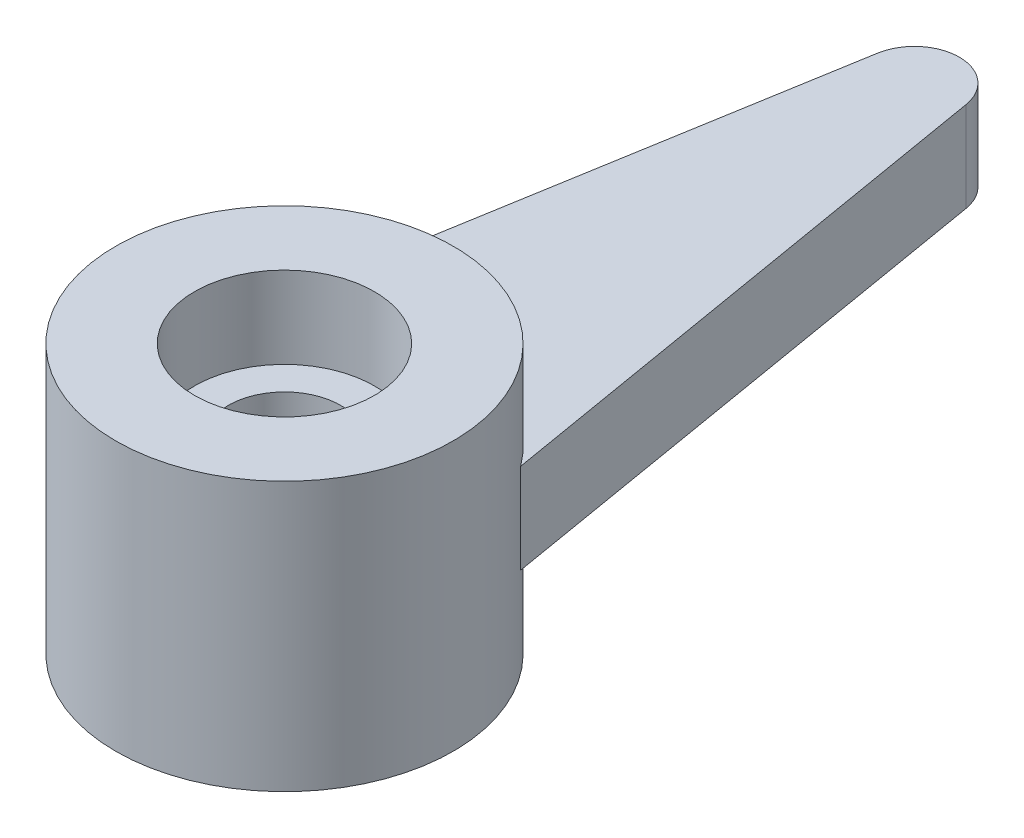
SolidWorks part; units mm, degrees
ref_plane "Front Plane" through (0, 0, 0) normal (0, 0, 1) x (1, 0, 0)
ref_plane "Top Plane" through (0, 0, 0) normal (0, 1, 0) x (1, 0, 0)
ref_plane "Right Plane" through (0, 0, 0) normal (1, 0, 0) x (0, 0, -1)
sketch "Sketch1" plane through (0, 0, 0) normal (0, 1, 0) x (1, 0, 0)
  line L0 (0, 0) -> (0, 22841.5203) construction
  line L1 (0, 0) -> (22841.5203, 0) construction
  circle A0 centre (0, 0) radius 7.5
  dimension "D1" = 15
extrude "Boss-Extrude1" add sketch "Sketch1" along normal mid plane 11.95
sketch "Sketch2" plane through (0, 5.975, 0) normal (0, 1, 0) x (1, 0, 0)
  circle A0 centre (0, 0) radius 2.5
  dimension "D1" = 5
extrude "Rod-Cutout" cut sketch "Sketch2" against normal through all and the other way through all
sketch "Sketch3" plane through (0, 5.975, 0) normal (0, 1, 0) x (1, 0, 0)
  circle A0 centre (0, 0) radius 4
  dimension "D1" = 8
extrude "Bearing-Cutout" cut sketch "Sketch3" against normal blind 3.63
mirror "Mirror1" about plane through (0, 0, 0) normal (0, 1, 0) of "Bearing-Cutout"
sketch "Sketch4" plane through (0, 0, 0) normal (0, 1, 0) x (1, 0, 0)
  line L0 (0, 0) -> (0, -50000) construction
  line L1 (0, 0) -> (-50000, 0) construction
  line L2 (-6, 0) -> (6, 0)
  line L3 (6, 0) -> (6, 4.5)
  line L4 (6, 4.5) -> (1.972, 28.3333)
  line L5 (-6, 0) -> (-6, 4.5)
  line L6 (-6, 4.5) -> (-1.972, 28.3333)
  circle A0 centre (0, 0) radius 7.5 construction
  arc A1 (1.972, 28.3333) -> (-1.972, 28.3333) centre (0, 28) ccw
  point P14 (0, 0)
  point P16 (4.4534, 18)
  point P17 (6.7782, 18)
  point P18 (6.9703, 18.0296)
  point P19 (8.939, 21.871)
  point P20 (1.9642, 18.5068)
  point P21 (2, 18.5928)
  point P22 (5.8906, 4.6422)
  point P23 (0, 0)
  point P24 (1.9854, 19.4676)
  point P26 (0, 0)
  dimension "D1" = 4
  dimension "D2" = 12
  dimension "D3" = 28
extrude "SteeringLink-Mount" add sketch "Sketch4" along normal mid plane 4
sketch "Sketch5" plane through (0, 5.975, 0) normal (0, 1, 0) x (1, 0, 0)
  circle A0 centre (0, 0) radius 2.5
  circle A1 centre (0, 0) radius 2.5 construction
extrude "Cut-Extrude3" cut sketch "Sketch5" against normal through all
